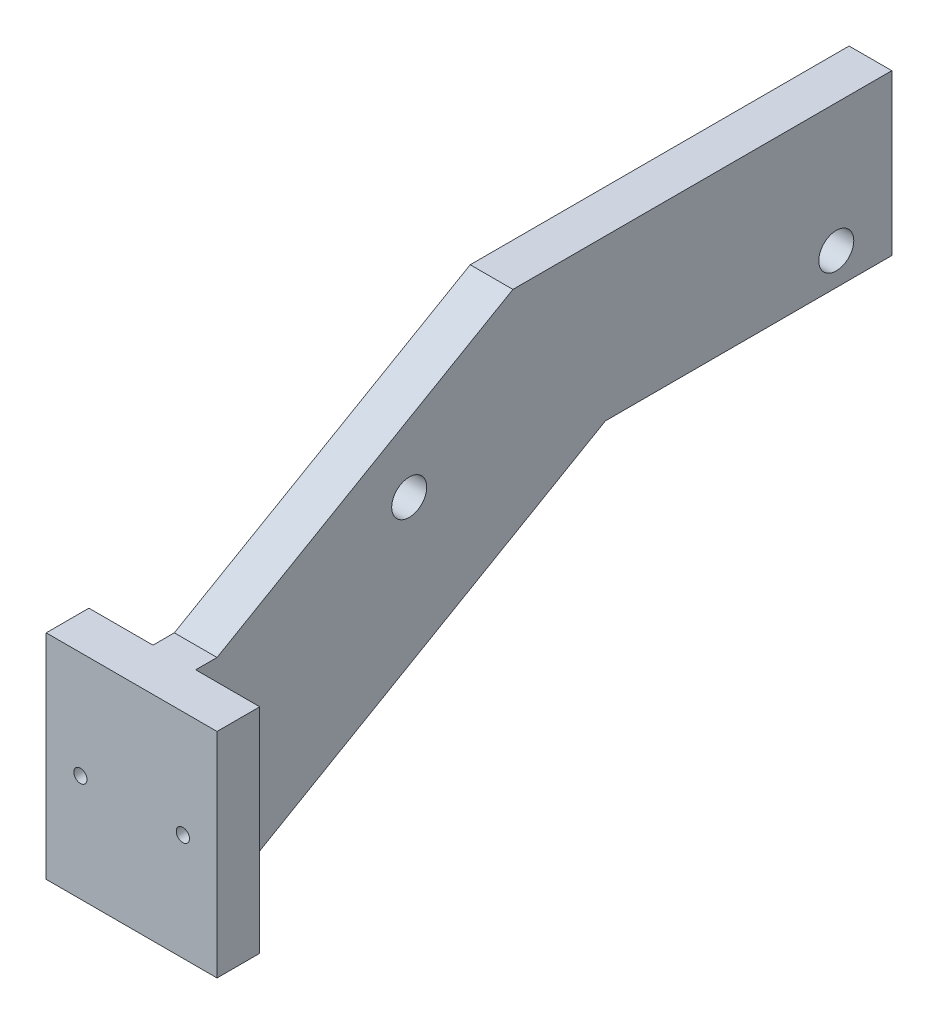
SolidWorks part; units mm, degrees
ref_plane "Alzado" through (0, 0, 0) normal (0, 0, 1) x (1, 0, 0)
ref_plane "Planta" through (0, 0, 0) normal (0, 1, 0) x (1, 0, 0)
ref_plane "Vista lateral" through (0, 0, 0) normal (1, 0, 0) x (0, 0, -1)
sketch "Croquis1" plane through (0, 0, 0) normal (1, 0, 0) x (0, 0, -1)
  line L0 (0, 0) -> (0, 50)
  line L1 (0, 50) -> (15, 50)
  line L2 (0, 0) -> (15, 0)
  line L3 (15, 0) -> (105.9327, 52.5)
  line L4 (15, 0) -> (40.1168, 0) construction
  line L5 (15, 50) -> (84.282, 90)
  line L7 (84.282, 90) -> (173.0021, 90)
  line L8 (173.0021, 90) -> (173.0021, 52.5)
  line L9 (173.0021, 52.5) -> (105.9327, 52.5)
  dimension "D1" = 50
  dimension "D2" = 15
  dimension "D3" = 30
  dimension "D4" = 15
  dimension "D5" = 80
  dimension "D6" = 67.0694
  dimension "D7" = 37.5
extrude "Saliente-Extruir1" add sketch "Croquis1" along normal blind 10
sketch "Croquis2" plane through (0, 0, 0) normal (0, 0, 1) x (1, 0, 0)
  line L0 (0, 50) -> (-15, 50)
  line L1 (-15, 50) -> (-15, 0)
  line L2 (-15, 0) -> (25, 0)
  line L3 (25, 0) -> (25, 50)
  line L4 (25, 50) -> (0, 50)
  dimension "D1" = 15
  dimension "D2" = 25
extrude "Saliente-Extruir2" add sketch "Croquis2" against normal blind 10
sketch "Croquis3" plane through (0, 0, 0) normal (0, 0, 1) x (1, 0, 0)
  circle A0 centre (-7, 25) radius 1.55
  circle A1 centre (17, 25) radius 1.55
  point P4 (0, 0)
  dimension "D2" = 3.1
  dimension "D3" = 3.1
  dimension "D1" = 24
  dimension "D4" = 8
  dimension "D5" = 25
extrude "Cortar-Extruir1" cut sketch "Croquis3" against normal blind 10
sketch "Croquis4" plane through (10, 0, 0) normal (1, 0, 0) x (0, 0, -1)
  circle A0 centre (60, 60) radius 4.1
  circle A1 centre (160, 60) radius 4.1
  point P4 (0, 0)
  dimension "D1" = 8.2
  dimension "D2" = 8.2
  dimension "D3" = 60
  dimension "D4" = 60
  dimension "D5" = 60
  dimension "D6" = 100
extrude "Cortar-Extruir2" cut sketch "Croquis4" against normal blind 10
